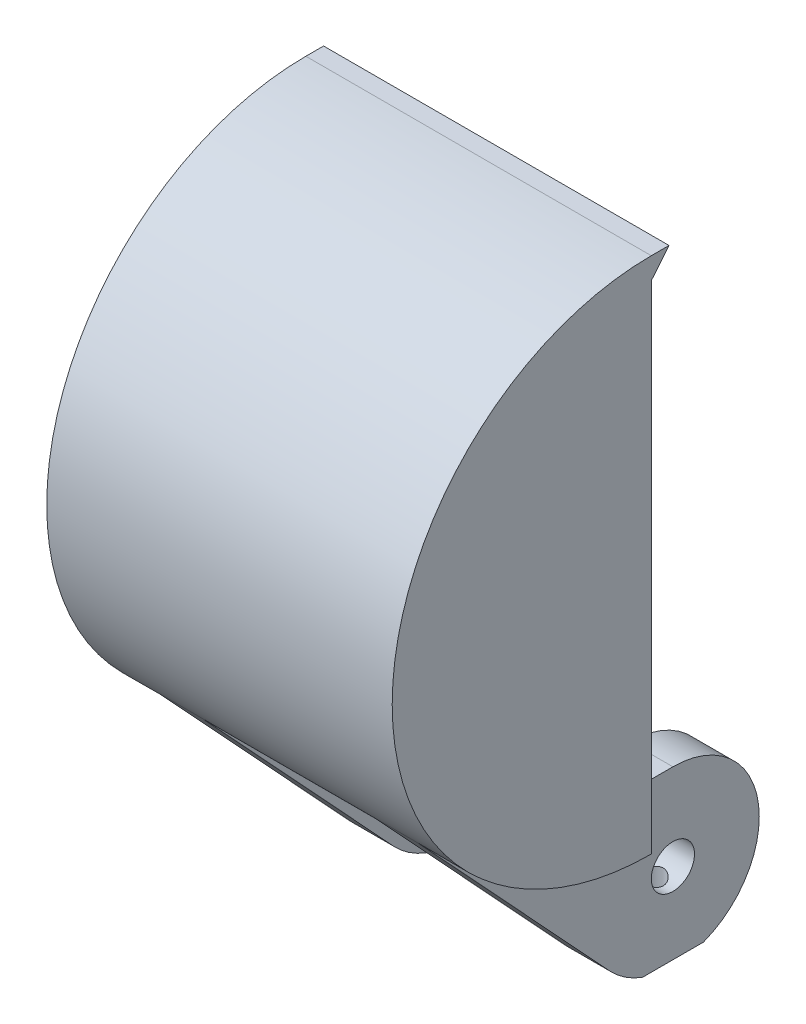
SolidWorks part; units mm, degrees
material "6061-T6 (SS)"
ref_plane "Front Plane" through (0, 0, 0) normal (0, 0, 1) x (1, 0, 0)
ref_plane "Top Plane" through (0, 0, 0) normal (0, 1, 0) x (1, 0, 0)
ref_plane "Right Plane" through (0, 0, 0) normal (1, 0, 0) x (0, 0, -1)
sketch "ExcavatorReferenceSize" plane through (0, 0, 0) normal (0, 1, 0) x (1, 0, 0)
  line L1 (-25.4, -12.7) -> (25.4, -12.7)
  line L2 (-25.4, -12.7) -> (-25.4, 12.7)
  line L3 (-25.4, 12.7) -> (25.4, 12.7)
  line L4 (25.4, -12.7) -> (25.4, 12.7)
  line L5 (-25.4, -12.7) -> (25.4, 12.7) construction
  line L6 (-25.4, 12.7) -> (25.4, -12.7) construction
  point P0 (0, 0)
  dimension "D1" = 25.4
  dimension "D2" = 50.8
sketch "Sketch2" plane through (0, 0, 0) normal (1, 0, 0) x (0, 0, -1)
  line L0 (0, 0) -> (0, 76.2)
  line L1 (0, 0) -> (8.9803, -8.9803) construction
  line L2 (0, 0) -> (0, 97.7406) construction
  arc A0 (0, 76.2) -> (0, 0) centre (0, 38.1) ccw
  dimension "D1" = 76.2
  dimension "D2" = 12.7
  dimension "D3" = 135
extrude "Boss-Extrude1" add sketch "Sketch2" along normal mid plane 50.8
shell "Shell1" thickness 3.175 removed face at (0, 38.1, 0)
chamfer "Chamfer1" [suppressed] distance 10 angle 45
sketch "Sketch4" plane through (0, 0, 0) normal (1, 0, 0) x (0, 0, -1)
  line L0 (0, 0) -> (31.6155, -31.6155) construction
  line L1 (0, 0) -> (0, 113.2937) construction
  circle A1 centre (9.525, -9.525) radius 12.7
  arc A2 (0, 73.025) -> (0, 3.175) centre (0, 38.1) ccw
  arc A3 (0, 73.025) -> (0, 3.175) centre (0, 38.1) ccw construction
  dimension "D1" = 25.4
  dimension "D2" = 135
  dimension "D3" = 12.7
extrude "Boss-Extrude3" add sketch "Sketch4" along normal mid plane 38.1
sketch "Sketch5" plane through (0, 0, 0) normal (1, 0, 0) x (0, 0, -1)
  line L1 (0, 3.175) -> (0, 0)
  line L3 (0, 0) -> (0, 76.2) construction
  line L4 (0, 3.175) -> (9.525, 3.175)
  line L5 (0, 0) -> (1.1247, 0)
  circle A0 centre (9.525, -9.525) radius 12.7 construction
  arc A1 (9.525, 3.175) -> (1.1247, 0) centre (9.525, -9.525) ccw
  dimension "D1" = 3.175
extrude "Boss-Extrude4" add sketch "Sketch5" along normal mid plane 38.1
sketch "Sketch6" plane through (0, 0, 0) normal (1, 0, 0) x (0, 0, -1)
  line L0 (0, 0) -> (12.9142, -12.9142) construction
  line L1 (0, 0) -> (0, 78.8833) construction
  circle A0 centre (9.525, -9.525) radius 12.7 construction
  circle A2 centre (9.525, -9.525) radius 12.7
  dimension "D1" = 225
extrude "Cut-Extrude2" cut sketch "Sketch6" against normal blind 12.7
extrude "Cut-Extrude3" cut sketch "Sketch6<2>" along normal blind 12.7
sketch "Sketch6<2>" plane through (0, 0, 0) normal (1, 0, 0) x (0, 0, -1) same geometry as "Sketch6"
sketch "Sketch7" plane through (-19.05, 0, 0) normal (-1, 0, 0) x (0, 0, 1)
  circle A2 centre (-9.525, -9.525) radius 12.7 construction
  circle A3 centre (-9.525, -9.525) radius 3.175
  circle A4 centre (-9.525, -9.525) radius 12.7 construction
  dimension "D1" = 6.35
extrude "Cut-Extrude4" cut sketch "Sketch7" against normal up to surface (38.1 mm away) up to face at (19.05, -4.1606, -4.835)
sketch "Sketch8" plane through (19.05, 0, 0) normal (1, 0, 0) x (0, 0, -1)
  line L3 (-27.9361, 12.1928) -> (0.213, -18.1607)
  line L6 (0.213, -18.1607) -> (5.0349, -21.4048)
  line L7 (-27.9361, 12.1928) -> (-25.2112, 13.9308)
  line L8 (5.0349, -21.4048) -> (1.1247, 0)
  line L9 (1.1247, 0) -> (0, 3.175)
  line L10 (0, 0) -> (4.7601, 0) construction
  circle A3 centre (9.525, -9.525) radius 12.7 construction
  arc A5 (0, 76.2) -> (0, 0) centre (0, 38.1) ccw construction
  arc A6 (-27.9361, 12.1928) -> (0, 0) centre (0, 38.1) ccw construction
  arc A7 (22.225, -9.525) -> (0.213, -18.1607) centre (9.525, -9.525) ccw construction
  arc A9 (0, 73.025) -> (0, 3.175) centre (0, 38.1) ccw
  arc A10 (-25.2112, 13.9308) -> (0, 3.175) centre (0, 38.1) ccw
  circle A11 centre (9.525, -9.525) radius 12.7 construction
  point P10 (1.1247, 0)
  point P11 (-27.9361, 12.1928)
  point P12 (0.213, -18.1607)
  point P18 (-25.2112, 13.9308)
extrude "Boss-Extrude5" add sketch "Sketch8" against normal up to surface (38.1 mm away) up to face at (-19.05, -9.525, -6.35)
ref_plane "Plane1" through (0, -21.4048, 0) normal (0, 1, 0) x (1, 0, 0)
sketch "Sketch9" plane through (0, 0, 0) normal (1, 0, 0) x (0, 0, -1)
  line L3 (9.525, 3.175) -> (0, 3.175)
  line L5 (0, 3.175) -> (0, 0)
  line L13 (0, 3.175) -> (0, 0)
  line L15 (-27.9361, 12.1928) -> (0.213, -18.1607)
  line L16 (-27.9361, 12.1928) -> (0.213, -18.1607)
  line L17 (9.525, 3.175) -> (0, 3.175)
  arc A2 (-27.9361, 12.1928) -> (0, 0) centre (0, 38.1) ccw
  arc A3 (0.213, -18.1607) -> (9.525, 3.175) centre (9.525, -9.525) ccw
  arc A9 (-27.9361, 12.1928) -> (0, 0) centre (0, 38.1) ccw
  arc A10 (0.213, -18.1607) -> (9.525, 3.175) centre (9.525, -9.525) ccw
  dimension "D1" = 0
extrude "Cut-Extrude5" cut sketch "Sketch9" against normal mid plane 25.4
sketch "Sketch11" plane through (0, 0, 0) normal (1, 0, 0) x (0, 0, -1)
  line L0 (0, 76.2) -> (0, 73.025)
  line L8 (9.525, -9.525) -> (1.3049, 74.6125) construction
  line L9 (0, 76.2) -> (2.6098, 76.2)
  line L10 (2.6098, 76.2) -> (0, 73.025)
  circle A2 centre (9.525, -9.525) radius 3.175 construction
  arc A4 (0, 76.2) -> (0, 0) centre (0, 38.1) ccw construction
  arc A5 (0, 76.2) -> (0, 0) centre (0, 38.1) ccw construction
  circle A6 centre (9.525, -9.525) radius 3.175 construction
  dimension "D1" = 45
extrude "Boss-Extrude6" add sketch "Sketch11" along normal mid plane 50.8 contours L10 L0 L9
ref_plane "Plane2" through (0, 73.025, 0) normal (0, -1, 0) x (-1, 0, 0)
fillet "Fillet2" radius 12.7 2 edges at (22.225, 38.1, 34.925) (-22.225, 38.1, 34.925)
sketch "Sketch12" plane through (0, -21.4048, 0) normal (0, 1, 0) x (1, 0, 0)
  line L1 (15.875, 12.7) -> (15.875, 6.35) construction
  line L2 (19.05, 0.213) -> (19.05, 22.225) construction
  line L3 (12.7, 22.225) -> (12.7, 0.213) construction
  line L4 (19.05, 0.213) -> (19.05, 22.225) construction
  line L5 (12.7, 22.225) -> (12.7, 0.213) construction
  line L6 (19.05, 11.219) -> (12.7, 11.219) construction
  line L7 (0, 0) -> (0, 34.6266) construction
  circle A0 centre (15.875, 9.525) radius 1.7526
  circle A1 centre (-15.875, 9.525) radius 1.7526
  point P4 (15.875, 9.525)
  point P13 (15.875, 11.219)
  dimension "D1" = 3.5052
extrude "Cut-Extrude6" cut sketch "Sketch12" along normal up to surface and the other way up to surface up to face at (19.05, -9.525, -12.7) other way up to face at (-15.875, -11.049, -13.0168)
sketch "Sketch13" plane through (0, -21.4048, 0) normal (0, 1, 0) x (1, 0, 0)
  line L0 (19.05, 15.875) -> (12.7, 15.875)
  line L2 (19.05, 15.875) -> (19.05, 3.175)
  line L3 (19.05, 3.175) -> (12.7, 3.175)
  line L4 (12.7, 10.3977) -> (12.7, 3.175)
  line L5 (12.7, 15.875) -> (12.7, 10.3977)
  line L6 (0, 0) -> (0, 23.3259) construction
  line L7 (-19.05, 15.875) -> (-12.7, 15.875)
  line L8 (-19.05, 15.875) -> (-19.05, 3.175)
  line L9 (-19.05, 3.175) -> (-12.7, 3.175)
  line L10 (-12.7, 10.3977) -> (-12.7, 3.175)
  line L11 (-12.7, 15.875) -> (-12.7, 10.3977)
  circle A0 centre (15.875, 9.525) radius 1.7526 construction
  circle A1 centre (15.875, 9.525) radius 1.7526 construction
  point P7 (15.875, 3.175)
  point P9 (19.05, 9.525)
  dimension "D1" = 12.7
  dimension "D2" = 6.35
extrude "Cut-Extrude7" cut sketch "Sketch13" against normal through all
